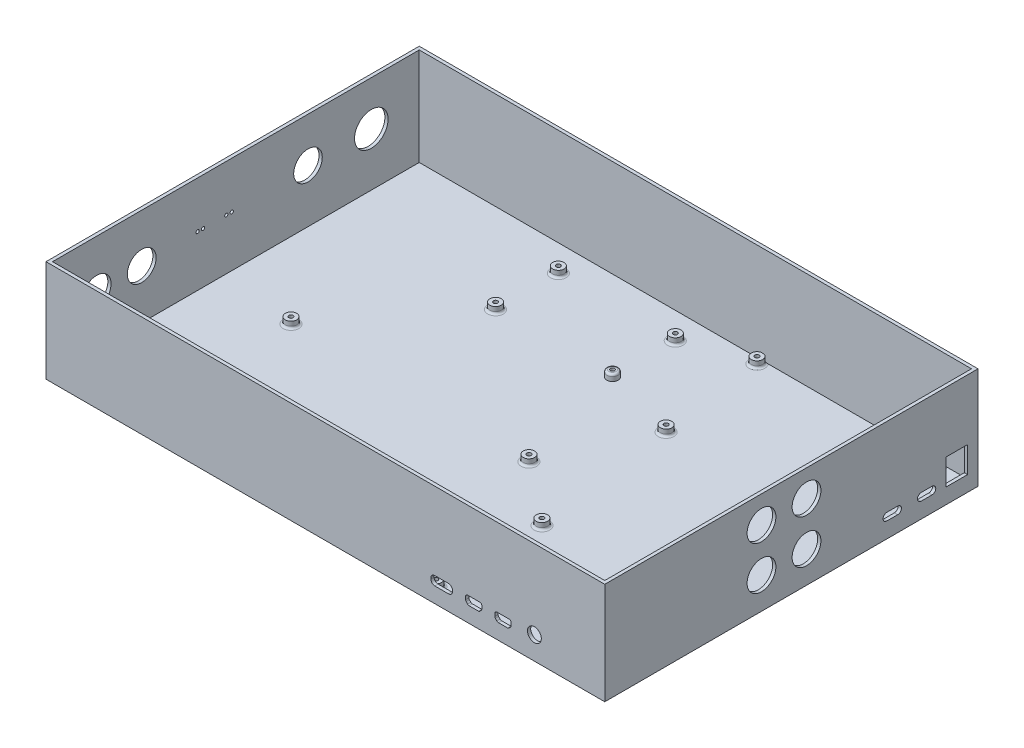
SolidWorks part; units mm, degrees
ref_plane "Front Plane" through (0, 0, 0) normal (0, 0, 1) x (1, 0, 0)
ref_plane "Top Plane" through (0, 0, 0) normal (0, 1, 0) x (1, 0, 0)
ref_plane "Right Plane" through (0, 0, 0) normal (1, 0, 0) x (0, 0, -1)
sketch "Sketch1" plane through (0, 0, 0) normal (0, -1, 0) x (1, 0, 0)
  line L0 (-24.0179, 95.5892) -> (-144.0179, 95.5892) construction
  line L1 (-174.0179, 95.5892) -> (80.9821, 95.5892)
  line L2 (-174.0179, 95.5892) -> (-174.0179, -73.7508)
  line L3 (-174.0179, -73.7508) -> (80.9821, -73.7508)
  line L4 (80.9821, 95.5892) -> (80.9821, -73.7508)
  line L5 (-24.0179, 95.5892) -> (-144.0179, 95.5892)
  line L6 (79.9821, -73.7508) -> (-17.0779, -73.7508) construction
  line L7 (79.9821, -73.7508) -> (-17.0779, -73.7508)
  line L8 (80.9821, -21.4108) -> (80.9821, -72.7508) construction
  line L9 (80.9821, -21.4108) -> (80.9821, -72.7508)
  line L10 (-144.0179, 95.5892) -> (-144.0179, 15.5892) construction
  line L11 (-144.0179, 95.5892) -> (-144.0179, 15.5892)
  dimension "D1" = 30
  dimension "D2" = 0
  dimension "D3" = 0
  dimension "D4" = 0
extrude "Boss-Extrude1" add sketch "Sketch1" along normal blind 2 from offset 4 contours L4 L3 L2 L1
sketch "Sketch2" plane through (0, -4, 0) normal (0, 1, 0) x (1, 0, 0)
  line L0 (-175.5179, 75.2508) -> (-175.5179, -97.0892)
  line L1 (-175.5179, -97.0892) -> (82.4821, -97.0892)
  line L2 (82.4821, -97.0892) -> (82.4821, 75.2508)
  line L3 (82.4821, 75.2508) -> (-175.5179, 75.2508)
  line L4 (-174.0179, -95.5892) -> (80.9821, -95.5892)
  line L5 (80.9821, -95.5892) -> (80.9821, 73.7508)
  line L6 (80.9821, 73.7508) -> (-174.0179, 73.7508)
  line L7 (-174.0179, 73.7508) -> (-174.0179, -95.5892)
  line L8 (-174.0179, -95.5892) -> (80.9821, -95.5892)
  line L9 (80.9821, -95.5892) -> (80.9821, 73.7508)
  line L10 (80.9821, 73.7508) -> (-174.0179, 73.7508)
  line L11 (-174.0179, 73.7508) -> (-174.0179, -95.5892)
  dimension "D1" = 0
  dimension "D2" = 1.5
extrude "Boss-Extrude2" add sketch "Sketch2" along normal blind 45 and the other way up to surface (2 mm away) other way up to face at (-46.5179, -6, 10.9192)
sketch "Sketch3" plane through (0, 0, 97.0892) normal (0, 0, 1) x (1, 0, 0)
  line L8 (4.0121, 1.1) -> (10.3521, 1.1)
  line L9 (12.1521, 2.9) -> (12.1521, 3.46)
  line L10 (10.3521, 5.26) -> (4.0121, 5.26)
  line L11 (2.2121, 3.46) -> (2.2121, 2.9)
  line L12 (4.0121, 1.1) -> (10.3521, 1.1)
  line L13 (12.1521, 2.9) -> (12.1521, 3.46)
  line L14 (10.3521, 5.26) -> (4.0121, 5.26)
  line L15 (2.2121, 3.46) -> (2.2121, 2.9)
  line L32 (21.8221, 1.1) -> (19.8266, 1.1)
  line L33 (19.1371, 1.3964) -> (18.4927, 2.0762)
  line L34 (18.2321, 2.7298) -> (18.2321, 4.05)
  line L35 (19.1821, 5) -> (24.7821, 5)
  line L36 (21.8221, 1.1) -> (19.8266, 1.1)
  line L37 (19.1371, 1.3964) -> (18.4927, 2.0762)
  line L38 (18.2321, 2.7298) -> (18.2321, 4.05)
  line L39 (19.1821, 5) -> (24.7821, 5)
  line L54 (22.1421, 1.1) -> (24.1376, 1.1)
  line L55 (24.827, 1.3964) -> (25.4715, 2.0762)
  line L56 (25.7321, 2.7298) -> (25.7321, 4.05)
  line L57 (22.1421, 1.1) -> (24.1376, 1.1)
  line L58 (24.827, 1.3964) -> (25.4715, 2.0762)
  line L59 (25.7321, 2.7298) -> (25.7321, 4.05)
  line L86 (35.6421, 1.1) -> (35.3221, 1.1)
  line L87 (39.2321, 4.05) -> (39.2321, 2.7298)
  line L88 (35.3221, 1.1) -> (33.3266, 1.1)
  line L89 (32.6371, 1.3964) -> (31.9927, 2.0762)
  line L90 (31.7321, 2.7298) -> (31.7321, 4.05)
  line L91 (32.6821, 5) -> (38.2821, 5)
  line L92 (39.2321, 4.05) -> (39.2321, 2.7298)
  line L93 (35.3221, 1.1) -> (33.3266, 1.1)
  line L94 (32.6371, 1.3964) -> (31.9927, 2.0762)
  line L95 (31.7321, 2.7298) -> (31.7321, 4.05)
  line L96 (32.6821, 5) -> (38.2821, 5)
  line L97 (22.1421, 1.1) -> (21.8221, 1.1)
  line L98 (35.6421, 1.1) -> (37.6376, 1.1)
  line L99 (38.327, 1.3964) -> (38.9715, 2.0762)
  line L100 (35.6421, 1.1) -> (37.6376, 1.1)
  line L101 (38.327, 1.3964) -> (38.9715, 2.0762)
  arc A8 (10.3521, 1.1) -> (12.1521, 2.9) centre (10.3521, 2.9) ccw
  arc A9 (12.1521, 3.46) -> (10.3521, 5.26) centre (10.3521, 3.46) ccw
  arc A10 (4.0121, 5.26) -> (2.2121, 3.46) centre (4.0121, 3.46) ccw
  arc A11 (2.2121, 2.9) -> (4.0121, 1.1) centre (4.0121, 2.9) ccw
  arc A12 (10.3521, 1.1) -> (12.1521, 2.9) centre (10.3521, 2.9) ccw
  arc A13 (12.1521, 3.46) -> (10.3521, 5.26) centre (10.3521, 3.46) ccw
  arc A14 (4.0121, 5.26) -> (2.2121, 3.46) centre (4.0121, 3.46) ccw
  arc A15 (2.2121, 2.9) -> (4.0121, 1.1) centre (4.0121, 2.9) ccw
  arc A27 (19.1371, 1.3964) -> (19.8266, 1.1) centre (19.8266, 2.05) ccw
  arc A28 (18.2321, 2.7298) -> (18.4927, 2.0762) centre (19.1821, 2.7298) ccw
  arc A29 (19.1821, 5) -> (18.2321, 4.05) centre (19.1821, 4.05) ccw
  arc A30 (19.1371, 1.3964) -> (19.8266, 1.1) centre (19.8266, 2.05) ccw
  arc A31 (18.2321, 2.7298) -> (18.4927, 2.0762) centre (19.1821, 2.7298) ccw
  arc A32 (19.1821, 5) -> (18.2321, 4.05) centre (19.1821, 4.05) ccw
  arc A53 (24.1376, 1.1) -> (24.827, 1.3964) centre (24.1376, 2.05) ccw
  arc A54 (25.4715, 2.0762) -> (25.7321, 2.7298) centre (24.7821, 2.7298) ccw
  arc A55 (25.7321, 4.05) -> (24.7821, 5) centre (24.7821, 4.05) ccw
  arc A56 (24.1376, 1.1) -> (24.827, 1.3964) centre (24.1376, 2.05) ccw
  arc A57 (25.4715, 2.0762) -> (25.7321, 2.7298) centre (24.7821, 2.7298) ccw
  arc A58 (25.7321, 4.05) -> (24.7821, 5) centre (24.7821, 4.05) ccw
  arc A80 (39.2321, 4.05) -> (38.2821, 5) centre (38.2821, 4.05) ccw
  arc A81 (32.6371, 1.3964) -> (33.3266, 1.1) centre (33.3266, 2.05) ccw
  arc A82 (31.7321, 2.7298) -> (31.9927, 2.0762) centre (32.6821, 2.7298) ccw
  arc A83 (32.6821, 5) -> (31.7321, 4.05) centre (32.6821, 4.05) ccw
  arc A84 (39.2321, 4.05) -> (38.2821, 5) centre (38.2821, 4.05) ccw
  arc A85 (32.6371, 1.3964) -> (33.3266, 1.1) centre (33.3266, 2.05) ccw
  arc A86 (31.7321, 2.7298) -> (31.9927, 2.0762) centre (32.6821, 2.7298) ccw
  arc A87 (32.6821, 5) -> (31.7321, 4.05) centre (32.6821, 4.05) ccw
  arc A92 (37.6376, 1.1) -> (38.327, 1.3964) centre (37.6376, 2.05) ccw
  arc A93 (38.9715, 2.0762) -> (39.2321, 2.7298) centre (38.2821, 2.7298) ccw
  arc A94 (37.6376, 1.1) -> (38.327, 1.3964) centre (37.6376, 2.05) ccw
  arc A95 (38.9715, 2.0762) -> (39.2321, 2.7298) centre (38.2821, 2.7298) ccw
  circle A96 centre (49.9821, 4.6) radius 3.2
  circle A97 centre (49.9821, 4.6) radius 3.2
  dimension "D1" = 0.5
  dimension "D2" = 0.5
  dimension "D3" = 0.5
  dimension "D4" = 0.5
  dimension "D5" = 0.5
  dimension "D6" = 0.5
extrude "Cut-Extrude1" cut sketch "Sketch3" against normal blind 30
sketch "Sketch4" plane through (82.4821, 0, 0) normal (1, 0, 0) x (0, 0, -1)
  line L0 (38.5008, 4.145) -> (32.8008, 4.145) construction
  line L1 (38.5008, 4.145) -> (32.8008, 4.145)
  line L2 (48.6758, 4.0894) -> (54.3758, 4.0894) construction
  line L3 (48.6758, 4.0894) -> (54.3758, 4.0894)
  line L4 (38.5008, 4.145) -> (48.6758, 4.0894)
  line L5 (43.5883, 4.1172) -> (43.5883, 5.0147)
  line L6 (35.6508, 4.145) -> (35.6508, 1.7159)
  line L7 (51.5258, 4.0894) -> (51.5258, 1.7512)
  line L8 (49.0258, 2.9203) -> (54.0258, 2.9203) construction
  line L9 (49.0258, 4.645) -> (54.0258, 4.645)
  line L10 (49.0258, 1.1956) -> (54.0258, 1.1956)
  line L11 (38.1508, 2.9203) -> (33.1508, 2.9203) construction
  line L12 (38.1508, 4.645) -> (33.1508, 4.645)
  line L13 (38.1508, 1.1956) -> (33.1508, 1.1956)
  line L22 (70.4488, 13.1) -> (60.4488, 13.1)
  line L23 (60.4488, 13.1) -> (60.4488, 1.1)
  line L24 (60.4488, 1.1) -> (70.4488, 1.1)
  line L25 (70.4488, 1.1) -> (70.4488, 13.1)
  line L26 (70.4488, 13.1) -> (60.4488, 13.1)
  line L27 (60.4488, 13.1) -> (60.4488, 1.1)
  line L28 (60.4488, 1.1) -> (70.4488, 1.1)
  line L29 (70.4488, 1.1) -> (70.4488, 13.1)
  arc A0 (49.0258, 4.645) -> (49.0258, 1.1956) centre (49.0258, 2.9203) ccw
  arc A1 (54.0258, 1.1956) -> (54.0258, 4.645) centre (54.0258, 2.9203) ccw
  arc A2 (38.1508, 4.645) -> (38.1508, 1.1956) centre (38.1508, 2.9203) cw
  arc A3 (33.1508, 1.1956) -> (33.1508, 4.645) centre (33.1508, 2.9203) cw
  point P12 (51.5258, 2.9203)
  point P19 (35.6508, 2.9203)
  dimension "D1" = 5
  dimension "D2" = 0.5
extrude "Cut-Extrude2" cut sketch "Sketch4" against normal blind 30 contours A3 L13 A2 L12 | L10 A1 L9 A0 | L28 L29 L26 L27 region at (82.4821, 4.4177, -48.3732) region at (82.4821, 2.2955, -39.66) region at (82.4821, 7.1, -65.4488)
sketch "Sketch5" plane through (82.4821, 0, 0) normal (1, 0, 0) x (0, 0, -1)
  arc A2 (-3.9298, 3.1042) -> (-3.9298, 13.9042) centre (-3.9298, 8.5042) ccw construction
  arc A3 (-3.9298, 3.1042) -> (-3.9298, 13.9042) centre (-3.9298, 8.5042) ccw
  arc A4 (-3.9298, 35.3458) -> (-3.9298, 22.0458) centre (-3.9298, 28.6958) ccw
  arc A5 (-3.9298, 22.0458) -> (-3.9298, 35.3458) centre (-3.9298, 28.6958) ccw
  arc A6 (-3.9298, 35.3458) -> (-3.9298, 22.0458) centre (-3.9298, 28.6958) ccw
  arc A7 (-3.9298, 22.0458) -> (-3.9298, 35.3458) centre (-3.9298, 28.6958) ccw
  arc A8 (-24.7298, 3.1042) -> (-24.7298, 13.9042) centre (-24.7298, 8.5042) ccw construction
  arc A9 (-24.7298, 3.1042) -> (-24.7298, 13.9042) centre (-24.7298, 8.5042) ccw
  circle A10 centre (-24.7298, 28.5042) radius 6.65
  circle A11 centre (-24.7298, 8.5042) radius 6.65
  circle A12 centre (-3.9298, 8.5042) radius 6.65
  spline S0 degree 3 poles (-357.9141, 1992.8223) (-188.5796, 669.6666) (-77.1426, 12.7262) (-23.5785, 22.0054) (-23.5551, 22.0096) (-23.1608, 22.0825) (-22.8013, 22.1812) (-22.4001, 22.3289) (-22.3521, 22.3471) (-21.9895, 22.4907) (-21.6902, 22.6363) (-21.3063, 22.8605) (-21.2135, 22.9178) (-20.7371, 23.2292) (-20.3848, 23.5154) (-19.7811, 24.119) (-19.5272, 24.4235) (-19.2685, 24.7977) (-19.2361, 24.846) (-18.9769, 25.2424) (-18.7832, 25.6106) (-18.6139, 26.023) (-18.603, 26.05) (-18.4455, 26.4477) (-18.3328, 26.8309) (-18.2499, 27.2507) (-18.2445, 27.2785) (-18.1665, 27.6999) (-18.1298, 28.1009) (-18.1297, 28.8824) (-18.162, 29.2579) (-18.2309, 29.6555) (-18.2351, 29.6789) (-18.308, 30.0732) (-18.4067, 30.4328) (-18.5544, 30.8339) (-18.5727, 30.8819) (-18.7162, 31.2445) (-18.8618, 31.5439) (-19.086, 31.9277) (-19.1433, 32.0206) (-19.4547, 32.4969) (-19.741, 32.8492) (-20.3445, 33.4529) (-20.6491, 33.7069) (-21.0232, 33.9655) (-21.0716, 33.9979) (-21.4679, 34.2571) (-21.8361, 34.4508) (-22.2485, 34.6202) (-22.2755, 34.631) (-22.6732, 34.7885) (-23.0564, 34.9012) (-23.4762, 34.9842) (-23.504, 34.9895) (-62.039, 42.1237) (-142.3083, -296.7412) (1675.1512, -981.7563) knots -4.179496 -4.179496 -4.179496 -4.179496 0.029297 0.029297 0.03125 0.03125 0.058594 0.058594 0.0625 0.0625 0.085938 0.085938 0.09375 0.09375 0.125 0.125 0.152344 0.152344 0.15625 0.15625 0.185547 0.185547 0.1875 0.1875 0.216797 0.216797 0.21875 0.21875 0.25 0.25 0.279297 0.279297 0.28125 0.28125 0.308594 0.308594 0.3125 0.3125 0.335938 0.335938 0.34375 0.34375 0.375 0.375 0.402344 0.402344 0.40625 0.40625 0.435547 0.435547 0.4375 0.4375 0.466797 0.466797 0.46875 0.46875 3.50318 3.50318 3.50318 3.50318 weights 1 1 1 1 1 1 1 1 1 1 1 1 1 1 1 1 1 1 1 1 1 1 1 1 1 1 1 1 1 1 1 1 1 1 1 1 1 1 1 1 1 1 1 1 1 1 1 1 1 1 1 1 1 1 1 1 1 1 only from (-24.7298, 21.9042) to (-24.7298, 35.1042) construction
  spline S1 degree 3 poles (-24.7298, 21.9042) (-24.3515, 21.9042) (-23.976, 21.9365) (-23.5785, 22.0054) (-23.5551, 22.0096) (-23.1608, 22.0825) (-22.8013, 22.1812) (-22.4001, 22.3289) (-22.3521, 22.3471) (-21.9895, 22.4907) (-21.6902, 22.6363) (-21.3063, 22.8605) (-21.2135, 22.9178) (-20.7371, 23.2292) (-20.3848, 23.5154) (-19.7811, 24.119) (-19.5272, 24.4235) (-19.2685, 24.7977) (-19.2361, 24.846) (-18.9769, 25.2424) (-18.7832, 25.6106) (-18.6139, 26.023) (-18.603, 26.05) (-18.4455, 26.4477) (-18.3328, 26.8309) (-18.2499, 27.2507) (-18.2445, 27.2785) (-18.1665, 27.6999) (-18.1298, 28.1009) (-18.1297, 28.8824) (-18.162, 29.2579) (-18.2309, 29.6555) (-18.2351, 29.6789) (-18.308, 30.0732) (-18.4067, 30.4328) (-18.5544, 30.8339) (-18.5727, 30.8819) (-18.7162, 31.2445) (-18.8618, 31.5439) (-19.086, 31.9277) (-19.1433, 32.0206) (-19.4547, 32.4969) (-19.741, 32.8492) (-20.3445, 33.4529) (-20.6491, 33.7069) (-21.0232, 33.9655) (-21.0716, 33.9979) (-21.4679, 34.2571) (-21.8361, 34.4508) (-22.2485, 34.6202) (-22.2755, 34.631) (-22.6732, 34.7885) (-23.0564, 34.9012) (-23.4762, 34.9842) (-23.504, 34.9895) (-23.9254, 35.0675) (-24.3264, 35.1042) (-24.7298, 35.1042) knots 0 0 0 0 0.029297 0.029297 0.03125 0.03125 0.058594 0.058594 0.0625 0.0625 0.085938 0.085938 0.09375 0.09375 0.125 0.125 0.152344 0.152344 0.15625 0.15625 0.185547 0.185547 0.1875 0.1875 0.216797 0.216797 0.21875 0.21875 0.25 0.25 0.279297 0.279297 0.28125 0.28125 0.308594 0.308594 0.3125 0.3125 0.335938 0.335938 0.34375 0.34375 0.375 0.375 0.402344 0.402344 0.40625 0.40625 0.435547 0.435547 0.4375 0.4375 0.466797 0.466797 0.46875 0.46875 0.5 0.5 0.5 0.5 weights 1 1 1 1 1 1 1 1 1 1 1 1 1 1 1 1 1 1 1 1 1 1 1 1 1 1 1 1 1 1 1 1 1 1 1 1 1 1 1 1 1 1 1 1 1 1 1 1 1 1 1 1 1 1 1 1 1 1
  dimension "D2" = 6.65
  dimension "D1" = 0.5
extrude "Cut-Extrude4" cut sketch "Sketch5" against normal blind 30 contours A10 | A11 | A12 | A6 A7 region at (82.4821, 28.6958, 3.9298) region at (82.4821, 28.5042, 24.7298) region at (82.4821, 8.5042, 24.7298) region at (82.4821, 8.5042, 3.9298)
sketch "Sketch6" plane through (-174.0179, 0, 0) normal (1, 0, 0) x (0, 0, -1)
  line L0 (-54.3892, 12.7658) -> (-54.3892, 24.6258)
  line L1 (-28.353, 19.2474) -> (-28.861, 19.7554)
  line L2 (-25.813, 19.2474) -> (-26.321, 19.7554)
  line L3 (-13.059, 19.7554) -> (-12.551, 19.2474)
  line L4 (-15.091, 19.2474) -> (-15.599, 19.7554)
  line L5 (-12.551, 19.2474) -> (-12.551, 19.7554)
  line L6 (-12.551, 19.7554) -> (-13.059, 19.7554)
  line L7 (-13.059, 19.7554) -> (-13.059, 19.2474)
  line L8 (-13.059, 19.2474) -> (-12.551, 19.2474)
  line L9 (-12.551, 19.2474) -> (-12.551, 19.7554)
  line L10 (-12.551, 19.7554) -> (-13.059, 19.7554)
  line L11 (-13.059, 19.7554) -> (-13.059, 19.2474)
  line L12 (-13.059, 19.2474) -> (-12.551, 19.2474)
  line L13 (-15.599, 19.7554) -> (-15.599, 19.2474)
  line L14 (-15.599, 19.2474) -> (-15.091, 19.2474)
  line L15 (-15.091, 19.2474) -> (-15.091, 19.7554)
  line L16 (-15.091, 19.7554) -> (-15.599, 19.7554)
  line L17 (-15.599, 19.7554) -> (-15.599, 19.2474)
  line L18 (-15.599, 19.2474) -> (-15.091, 19.2474)
  line L19 (-15.091, 19.2474) -> (-15.091, 19.7554)
  line L20 (-15.091, 19.7554) -> (-15.599, 19.7554)
  line L21 (-25.813, 19.2474) -> (-25.813, 19.7554)
  line L22 (-25.813, 19.7554) -> (-26.321, 19.7554)
  line L23 (-26.321, 19.7554) -> (-26.321, 19.2474)
  line L24 (-26.321, 19.2474) -> (-25.813, 19.2474)
  line L25 (-25.813, 19.2474) -> (-25.813, 19.7554)
  line L26 (-25.813, 19.7554) -> (-26.321, 19.7554)
  line L27 (-26.321, 19.7554) -> (-26.321, 19.2474)
  line L28 (-26.321, 19.2474) -> (-25.813, 19.2474)
  line L29 (-28.861, 19.7554) -> (-28.861, 19.2474)
  line L30 (-28.861, 19.2474) -> (-28.353, 19.2474)
  line L31 (-28.353, 19.2474) -> (-28.353, 19.7554)
  line L32 (-28.353, 19.7554) -> (-28.861, 19.7554)
  line L33 (-28.861, 19.7554) -> (-28.861, 19.2474)
  line L34 (-28.861, 19.2474) -> (-28.353, 19.2474)
  line L35 (-28.353, 19.2474) -> (-28.353, 19.7554)
  line L36 (-28.353, 19.7554) -> (-28.861, 19.7554)
  circle A0 centre (-54.3892, 18.6958) radius 6.65
  circle A1 centre (-75.1892, 18.6958) radius 6.65
  arc A2 (-75.1892, 16.1958) -> (-75.1892, 21.1958) centre (-75.1892, 18.6958) ccw construction
  arc A3 (-75.1892, 16.1958) -> (-75.1892, 21.1958) centre (-75.1892, 18.6958) ccw
  circle A5 centre (51.6265, 20.5) radius 8.75 construction
  arc A6 (21.8151, 16.0167) -> (21.8555, 16.0118) centre (22.3777, 20.5) ccw
  arc A7 (-54.3892, 13.8458) -> (-54.3892, 23.5458) centre (-54.3892, 18.6958) ccw construction
  circle A8 centre (22.3777, 20.5) radius 6.6
  circle A10 centre (51.6265, 20.5) radius 8.75 construction
  circle A11 centre (22.3777, 20.5) radius 7.6 construction
  circle A12 centre (22.3777, 20.5) radius 7.6 construction
  arc A13 (-54.3892, 13.8458) -> (-54.3892, 23.5458) centre (-54.3892, 18.6958) ccw
  circle A14 centre (-75.1892, 18.6958) radius 6.65
  circle A15 centre (51.6265, 20.5) radius 7.75
  circle A16 centre (-26.067, 19.5014) radius 0.75
  circle A17 centre (-28.607, 19.5014) radius 0.75
  circle A18 centre (-15.345, 19.5014) radius 0.75
  circle A19 centre (-12.805, 19.5014) radius 0.75
  spline S1 degree 3 poles (-69.2251, 37.9448) (-68.8468, 37.9448) (-68.4713, 37.9125) (-68.0738, 37.8436) (-68.0504, 37.8394) (-67.6561, 37.7665) (-67.2966, 37.6679) (-66.8954, 37.5202) (-66.8474, 37.5019) (-66.4848, 37.3583) (-66.1854, 37.2128) (-65.8016, 36.9886) (-65.7087, 36.9312) (-65.2324, 36.6198) (-64.8801, 36.3336) (-64.2764, 35.73) (-64.0224, 35.4255) (-63.7638, 35.0513) (-63.7314, 35.003) (-63.4722, 34.6066) (-63.2785, 34.2384) (-63.1092, 33.826) (-63.0983, 33.799) (-62.9408, 33.4013) (-62.8281, 33.0181) (-62.7452, 32.5983) (-62.7398, 32.5705) (-62.6618, 32.1491) (-62.6251, 31.7481) (-62.625, 30.9666) (-62.6573, 30.5912) (-62.7262, 30.1935) (-62.7304, 30.1701) (-62.8033, 29.7758) (-62.902, 29.4163) (-63.0497, 29.0151) (-63.068, 28.9671) (-63.2115, 28.6045) (-63.3571, 28.3051) (-63.5813, 27.9213) (-63.6386, 27.8284) (-63.95, 27.3521) (-64.2363, 26.9998) (-64.8398, 26.3961) (-65.1444, 26.1421) (-65.5185, 25.8835) (-65.5668, 25.8511) (-65.9632, 25.5919) (-66.3314, 25.3982) (-66.7438, 25.2289) (-66.7708, 25.218) (-67.1685, 25.0605) (-67.5517, 24.9478) (-67.9715, 24.8649) (-67.9993, 24.8595) (-68.4207, 24.7815) (-68.8217, 24.7448) (-69.2251, 24.7448) knots 0 0 0 0 0.029297 0.029297 0.03125 0.03125 0.058594 0.058594 0.0625 0.0625 0.085938 0.085938 0.09375 0.09375 0.125 0.125 0.152344 0.152344 0.15625 0.15625 0.185547 0.185547 0.1875 0.1875 0.216797 0.216797 0.21875 0.21875 0.25 0.25 0.279297 0.279297 0.28125 0.28125 0.308594 0.308594 0.3125 0.3125 0.335938 0.335938 0.34375 0.34375 0.375 0.375 0.402344 0.402344 0.40625 0.40625 0.435547 0.435547 0.4375 0.4375 0.466797 0.466797 0.46875 0.46875 0.5 0.5 0.5 0.5 weights 1 1 1 1 1 1 1 1 1 1 1 1 1 1 1 1 1 1 1 1 1 1 1 1 1 1 1 1 1 1 1 1 1 1 1 1 1 1 1 1 1 1 1 1 1 1 1 1 1 1 1 1 1 1 1 1 1 1
  spline S3 degree 3 poles (-90.0251, 37.9448) (-89.6468, 37.9448) (-89.2713, 37.9125) (-88.8738, 37.8436) (-88.8504, 37.8394) (-88.4561, 37.7665) (-88.0966, 37.6679) (-87.6954, 37.5202) (-87.6474, 37.5019) (-87.2848, 37.3583) (-86.9854, 37.2128) (-86.6016, 36.9886) (-86.5087, 36.9312) (-86.0324, 36.6198) (-85.6801, 36.3336) (-85.0764, 35.73) (-84.8224, 35.4255) (-84.5638, 35.0513) (-84.5314, 35.003) (-84.2722, 34.6066) (-84.0785, 34.2384) (-83.9092, 33.826) (-83.8983, 33.799) (-83.7408, 33.4013) (-83.6281, 33.0181) (-83.5452, 32.5983) (-83.5398, 32.5705) (-83.4618, 32.1491) (-83.4251, 31.7481) (-83.425, 30.9666) (-83.4573, 30.5912) (-83.5262, 30.1935) (-83.5304, 30.1701) (-83.6033, 29.7758) (-83.702, 29.4163) (-83.8497, 29.0151) (-83.868, 28.9671) (-84.0115, 28.6045) (-84.1571, 28.3051) (-84.3813, 27.9213) (-84.4386, 27.8284) (-84.75, 27.3521) (-85.0363, 26.9998) (-85.6398, 26.3961) (-85.9444, 26.1421) (-86.3185, 25.8835) (-86.3668, 25.8511) (-86.7632, 25.5919) (-87.1314, 25.3982) (-87.5438, 25.2289) (-87.5708, 25.218) (-87.9685, 25.0605) (-88.3517, 24.9478) (-88.7715, 24.8649) (-88.7993, 24.8595) (-89.2207, 24.7815) (-89.6217, 24.7448) (-90.0251, 24.7448) knots 0 0 0 0 0.029297 0.029297 0.03125 0.03125 0.058594 0.058594 0.0625 0.0625 0.085938 0.085938 0.09375 0.09375 0.125 0.125 0.152344 0.152344 0.15625 0.15625 0.185547 0.185547 0.1875 0.1875 0.216797 0.216797 0.21875 0.21875 0.25 0.25 0.279297 0.279297 0.28125 0.28125 0.308594 0.308594 0.3125 0.3125 0.335938 0.335938 0.34375 0.34375 0.375 0.375 0.402344 0.402344 0.40625 0.40625 0.435547 0.435547 0.4375 0.4375 0.466797 0.466797 0.46875 0.46875 0.5 0.5 0.5 0.5 weights 1 1 1 1 1 1 1 1 1 1 1 1 1 1 1 1 1 1 1 1 1 1 1 1 1 1 1 1 1 1 1 1 1 1 1 1 1 1 1 1 1 1 1 1 1 1 1 1 1 1 1 1 1 1 1 1 1 1
  point P23 (-54.3892, 18.6958)
  point P52 (0, 0)
  dimension "D1" = 13.3
  dimension "D2" = 1
  dimension "D8" = 1.5
  dimension "D3" = 1
  dimension "D4" = 0
  dimension "D5" = 0
  dimension "D6" = 0
  dimension "D7" = 0
extrude "Cut-Extrude6" cut sketch "Sketch6" against normal blind 30 contours A15 | A8 | A0 A13 L0 | L0 A13 | A1 | L27 L28 L2 | L25 L26 L2 | A16 L28 L27 L26 L25 | A17 L36 L35 L34 L33 | L35 L36 L1 | L33 L34 L1 | A19 L12 L11 L10 L9 | L11 L12 L3 | L9 L10 L3 | A18 L20 L19 L18 L17 | L17 L18 L4 | L19 L20 L4 region at (-174.0179, 18.6958, 52.3308) region at (-174.0179, 19.4167, 28.6917) region at (-174.0179, 19.5861, 28.5223) region at (-174.0179, 19.4167, 26.1517) region at (-174.0179, 19.5861, 25.9823) region at (-174.0179, 19.5861, 12.7204) region at (-174.0179, 19.4167, 12.8897) region at (-174.0179, 19.4167, 15.4297) region at (-174.0179, 19.5861, 15.2604) region at (-174.0179, 18.6958, 55.135) region at (-174.0179, 18.6958, 75.1892) region at (-174.0179, 20.5, -22.3777) region at (-174.0179, 20.5, -51.6265) region at (-174.0179, 19.5014, 26.7958) region at (-174.0179, 19.5014, 29.3358) region at (-174.0179, 19.5014, 16.0738) region at (-174.0179, 19.5014, 13.5338)
sketch "Sketch7" plane through (0, -4, 0) normal (0, 1, 0) x (1, 0, 0)
  circle A0 centre (-29.0179, -20.5892) radius 1.6 construction
  circle A1 centre (-29.0179, -20.5892) radius 1.6 construction
  circle A2 centre (-29.0179, -90.5892) radius 1.6 construction
  circle A3 centre (-29.0179, -90.5892) radius 1.6 construction
  circle A4 centre (-139.0179, -90.5892) radius 1.6 construction
  circle A5 centre (-139.0179, -90.5892) radius 1.6 construction
  circle A6 centre (-139.0179, -20.5892) radius 1.6 construction
  circle A7 centre (-139.0179, -20.5892) radius 1.6 construction
  circle A8 centre (-97.6179, 32.5808) radius 2 construction
  circle A9 centre (-97.6179, 32.5808) radius 2 construction
  circle A10 centre (-97.6179, 61.5808) radius 2 construction
  circle A11 centre (-97.6179, 61.5808) radius 2 construction
  circle A12 centre (-43.6179, 61.5808) radius 2 construction
  circle A14 centre (-43.6179, 61.5808) radius 2 construction
  circle A24 centre (-0.5179, -43.0892) radius 1.35 construction
  circle A25 centre (-0.5179, -43.0892) radius 1.35 construction
  circle A26 centre (-0.5179, -92.0892) radius 1.35 construction
  circle A27 centre (-0.5179, -92.0892) radius 1.35 construction
  circle A28 centre (57.4821, -92.0892) radius 1.35 construction
  circle A29 centre (57.4821, -92.0892) radius 1.35 construction
  circle A30 centre (57.4821, -43.0892) radius 1.35 construction
  circle A31 centre (57.4821, -43.0892) radius 1.35 construction
  circle A32 centre (65.7421, 22.9508) radius 1.5998 construction
  circle A33 centre (67.0121, 71.2108) radius 1.5998 construction
  circle A34 centre (-15.5379, 71.2108) radius 1.5998 construction
  circle A35 centre (-9.2292, 22.9508) radius 1.5694 construction
  circle A36 centre (-43.6179, 32.5808) radius 1.2072 construction
  circle A37 centre (-29.0179, -90.5892) radius 0.9846
  circle A38 centre (-29.0179, -90.5892) radius 2.619
  circle A39 centre (-0.5179, -43.0892) radius 0.9846
  circle A40 centre (-0.5179, -43.0892) radius 2.619
  circle A41 centre (57.4821, -43.0892) radius 2.619
  circle A42 centre (57.4821, -43.0892) radius 0.9846
  circle A43 centre (65.7421, 22.9508) radius 0.9846
  circle A44 centre (65.7421, 22.9508) radius 2.619
  circle A45 centre (67.0121, 71.2108) radius 2.619
  circle A46 centre (67.0121, 71.2108) radius 0.9846
  circle A47 centre (-29.0179, -20.5892) radius 2.619
  circle A48 centre (-29.0179, -20.5892) radius 0.9846
  circle A49 centre (-9.2292, 22.9508) radius 2.619
  circle A50 centre (-9.2292, 22.9508) radius 0.9846
  circle A51 centre (-43.6179, 32.5808) radius 0.9846
  circle A52 centre (-43.6179, 32.5808) radius 2.619
  circle A53 centre (-43.6179, 61.5808) radius 2.619
  circle A54 centre (-43.6179, 61.5808) radius 0.9846
  circle A55 centre (-97.6179, 32.5808) radius 0.9846
  circle A56 centre (-97.6179, 32.5808) radius 2.619
  circle A57 centre (-97.6179, 61.5808) radius 0.9846
  circle A58 centre (-97.6179, 61.5808) radius 2.619
  circle A59 centre (-139.0179, -20.4747) radius 2.619
  circle A60 centre (-139.0179, -20.4747) radius 0.9846
  circle A61 centre (-139.0179, -90.5892) radius 2.619
  circle A62 centre (-139.0179, -90.5892) radius 0.9846
  circle A63 centre (-15.5379, 71.2108) radius 2.619
  circle A64 centre (-15.5379, 71.2108) radius 0.9846
  circle A65 centre (-0.5179, -92.0892) radius 0.9846
  circle A66 centre (-0.5179, -92.0892) radius 2.619
  circle A67 centre (57.4821, -92.0892) radius 0.9846
  circle A68 centre (57.4821, -92.0892) radius 2.619
  dimension "D1" = 1.9692
  dimension "D2" = 5.238
extrude "Boss-Extrude3" add sketch "Sketch7" along normal blind 3
fillet "Fillet1" radius 1 16 edges at (-29.0179, -4, 93.2082) (-43.6179, -1, -29.9618) (57.4821, -1, 45.7082) (-0.5179, -4, 45.7082) (-139.0179, -4, 93.2082) (-139.0179, -4, 23.0937) (65.7421, -4, -20.3318) (67.0121, -4, -68.5918) (-9.2292, -4, -20.3318) (-29.0179, -4, 23.2082) (-97.6179, -4, -58.9618) (-97.6179, -4, -29.9618) (-15.5379, -4, -68.5918) (-43.6179, -4, -58.9618) (57.4821, -4, 94.7082) (-0.5179, -4, 94.7082)
